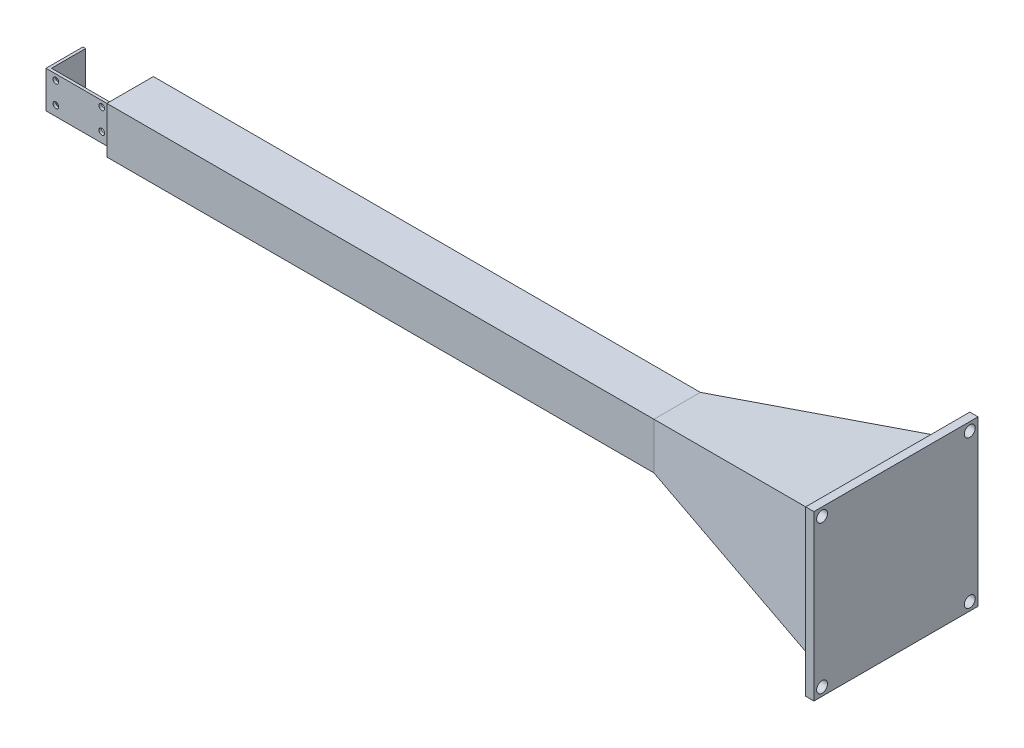
SolidWorks part; units mm, degrees
material "1023 Carbon Steel Sheet (SS)"
ref_plane "Front Plane" through (0, 0, 0) normal (0, 0, 1) x (1, 0, 0)
ref_plane "Top Plane" through (0, 0, 0) normal (0, 1, 0) x (1, 0, 0)
ref_plane "Right Plane" through (0, 0, 0) normal (1, 0, 0) x (0, 0, -1)
sketch "Sketch1" plane through (0, 0, 0) normal (0, 0, 1) x (1, 0, 0)
  line L264 (-103.7607, 63.7322) -> (-103.7607, -66.2678)
  line L265 (116.2393, 63.7322) -> (116.2393, -66.2678)
  line L267 (116.2393, 63.7322) -> (-103.7607, 63.7322)
  line L269 (116.2393, -66.2678) -> (-103.7607, -66.2678)
  circle A2 centre (90.2393, -40.2678) radius 10.5
  circle A3 centre (-77.7607, -40.2678) radius 10.5
  circle A4 centre (-77.7607, 37.7322) radius 10.5
  circle A5 centre (90.2393, 37.7322) radius 10.5
extrude "Boss-Extrude1" add sketch "Sketch1" along normal blind 10
sketch "Sketch2" plane through (0, 0, 10) normal (0, 0, 1) x (1, 0, 0)
  line L3 (-103.7607, 63.7322) -> (-113.7607, 63.7322)
  line L4 (-103.7607, 63.7322) -> (-103.7607, -66.2678)
  line L6 (-113.7607, 63.7322) -> (-113.7607, -66.2678)
  line L7 (-103.7607, -66.2678) -> (116.2393, -66.2678)
  line L8 (-113.7607, -66.2678) -> (-113.7607, -76.2678)
  line L9 (-113.7607, -76.2678) -> (116.2393, -76.2678)
  line L10 (116.2393, -66.2678) -> (116.2393, -76.2678)
extrude "Boss-Extrude2" add sketch "Sketch2" against normal blind 250
sketch "Sketch3" plane through (0, 63.7322, 0) normal (0, 1, 0) x (1, 0, 0)
  line L6 (116.2393, 0) -> (-103.7607, 0)
  line L7 (-103.7607, 0) -> (-103.7607, 240)
  line L8 (-103.7607, 240) -> (-113.7607, 240)
  line L9 (-113.7607, 240) -> (-113.7607, -10)
  line L10 (-113.7607, -10) -> (116.2393, -10)
  line L11 (116.2393, -10) -> (116.2393, 0)
  line L12 (116.2393, 0) -> (-103.7607, 0)
  line L13 (-103.7607, 0) -> (-103.7607, 240)
  line L14 (-103.7607, 240) -> (-113.7607, 240)
  line L15 (-113.7607, 240) -> (-113.7607, -10)
  line L16 (-113.7607, -10) -> (116.2393, -10)
  line L17 (116.2393, -10) -> (116.2393, 0)
  dimension "D1" = 0
extrude "Cut-Extrude1" cut sketch "Sketch3" against normal blind 5
sketch "Sketch4" plane through (0, 0, 10) normal (0, 0, 1) x (1, 0, 0)
  line L0 (-113.7607, -76.2678) -> (116.2393, -76.2678) construction
  line L1 (-113.7607, -76.2678) -> (116.2393, -76.2678)
  line L3 (116.2393, 58.7322) -> (126.2393, 58.7322)
  line L4 (116.2393, 58.7322) -> (116.2393, -76.2678)
  line L5 (116.2393, -76.2678) -> (126.2393, -76.2678)
  line L6 (126.2393, 58.7322) -> (126.2393, -76.2678)
  line M5 (116.2393, -76.2678) -> (116.2393, 58.7322)
extrude "Boss-Extrude3" add sketch "Sketch4" against normal up to surface (250 mm away) contours L6 L3 L5 M5 region at (121.2393, -8.7678, 10) up to face at (-33.7607, -27.9344, -240)
sketch "Sketch5" plane through (126.2393, 0, 0) normal (1, 0, 0) x (0, 0, -1)
  line L4 (240, -76.2678) -> (240, 58.7322)
  line L5 (240, 58.7322) -> (-10, 58.7322)
  line L6 (-10, 58.7322) -> (-10, -76.2678)
  line L7 (-10, -76.2678) -> (240, -76.2678)
  line L8 (240, -76.2678) -> (240, 58.7322)
  line L9 (240, 58.7322) -> (-10, 58.7322)
  line L10 (-10, 58.7322) -> (-10, -76.2678)
  line L11 (-10, -76.2678) -> (240, -76.2678)
  dimension "D1" = 0
extrude "Boss-Extrude4" add sketch "Sketch5" along normal blind 2800 separate body
sketch "Sketch8" plane through (2926.2393, 0, 0) normal (1, 0, 0) x (0, 0, -1)
  line L0 (-10, -76.2678) -> (240, -76.2678) construction
  line L1 (-10, 58.7322) -> (125, 58.7322)
  line L2 (-10, 58.7322) -> (-10, -76.2678)
  line L3 (-10, -76.2678) -> (125, -76.2678)
  line L4 (125, 58.7322) -> (125, -76.2678)
  line L6 (125, 58.7322) -> (240, 58.7322)
  line L7 (125, 58.7322) -> (125, -76.2678)
  line L8 (125, -76.2678) -> (240, -76.2678)
  line L9 (240, 58.7322) -> (240, -76.2678)
  line M9 (-10, -76.2678) -> (240, -76.2678)
  line M10 (240, -76.2678) -> (240, 58.7322)
  line M11 (240, 58.7322) -> (-10, 58.7322)
extrude "Cut-Extrude2" cut sketch "Sketch8" against normal blind 10000 contours L4 M11 M9 M10 region at (2926.2393, -8.7678, -182.5)
sketch "Sketch12" plane through (2926.2393, 0, 0) normal (1, 0, 0) x (0, 0, -1)
  line L2 (-27.5, 76.2322) -> (142.5, 76.2322)
  line L3 (-27.5, 76.2322) -> (-27.5, -93.7678)
  line L4 (-27.5, -93.7678) -> (142.5, -93.7678)
  line L5 (142.5, 76.2322) -> (142.5, -93.7678)
  line L6 (-27.5, 76.2322) -> (142.5, -93.7678) construction
  line L7 (-27.5, -93.7678) -> (142.5, 76.2322) construction
  point P4 (57.5, -8.7678)
extrude "Boss-Extrude6" add sketch "Sketch12" against normal up to vertex (2800 mm away) up to point (126.2393, 58.7322, 10)
sketch "Sketch14" plane through (0, -76.2678, 0) normal (0, -1, 0) x (1, 0, 0)
  line L0 (-103.7607, 0) -> (116.2393, 0)
  line L5 (116.2393, 0) -> (116.2393, -115)
  line L7 (-103.7607, 0) -> (-103.7607, -115)
  line L8 (116.2393, -115) -> (116.2393, -125)
  line L12 (116.2393, -125) -> (-103.7607, -125)
  line L13 (-103.7607, -125) -> (-103.7607, -115)
extrude "Cut-Extrude3" cut sketch "Sketch14" against normal blind 50
ref_plane "Plane3" through (2126.2393, 0, 0) normal (1, 0, 0) x (0, 0, -1)
sketch "Sketch15" plane through (2126.2393, 0, 0) normal (1, 0, 0) x (0, 0, -1)
  line L4 (142.5, -93.7678) -> (142.5, 76.2322)
  line L5 (142.5, 76.2322) -> (-27.5, 76.2322)
  line L6 (-27.5, 76.2322) -> (-27.5, -93.7678)
  line L7 (-27.5, -93.7678) -> (142.5, -93.7678)
  line L8 (142.5, -93.7678) -> (142.5, 76.2322)
  line L9 (142.5, 76.2322) -> (-27.5, 76.2322)
  line L10 (-27.5, 76.2322) -> (-27.5, -93.7678)
  line L11 (-27.5, -93.7678) -> (142.5, -93.7678)
  dimension "D1" = 0
sketch "Sketch16" plane through (2926.2393, 0, 0) normal (1, 0, 0) x (0, 0, -1)
  line L2 (307.5, 241.2322) -> (-192.5, 241.2322)
  line L3 (307.5, 241.2322) -> (307.5, -258.7678)
  line L4 (307.5, -258.7678) -> (-192.5, -258.7678)
  line L5 (-192.5, 241.2322) -> (-192.5, -258.7678)
  point P0 (0, 0)
loft "Loft3" add profiles "Sketch15", "Sketch16" connector at (2126.2393, -93.7678, 27.5) connector at (2926.2393, -258.7678, 192.5)
sketch "Sketch17" plane through (2926.2393, 0, 0) normal (1, 0, 0) x (0, 0, -1)
  line L2 (-242.5, 291.2322) -> (357.5, 291.2322)
  line L3 (-242.5, 291.2322) -> (-242.5, -308.7678)
  line L4 (-242.5, -308.7678) -> (357.5, -308.7678)
  line L5 (357.5, 291.2322) -> (357.5, -308.7678)
  line L6 (-242.5, 291.2322) -> (357.5, -308.7678) construction
  line L7 (-242.5, -308.7678) -> (357.5, 291.2322) construction
  point P4 (57.5, -8.7678)
extrude "Boss-Extrude7" add sketch "Sketch17" against normal blind 30
sketch "Sketch18" plane through (2926.2393, 0, 0) normal (1, 0, 0) x (0, 0, -1)
  circle A0 centre (-212.5, 261.2322) radius 20
  circle A1 centre (327.5, 261.2322) radius 20
  circle A2 centre (327.5, -278.7678) radius 20
  circle A3 centre (-212.5, -278.7678) radius 20
extrude "Cut-Extrude4" cut sketch "Sketch18" against normal through all both and the other way through all
